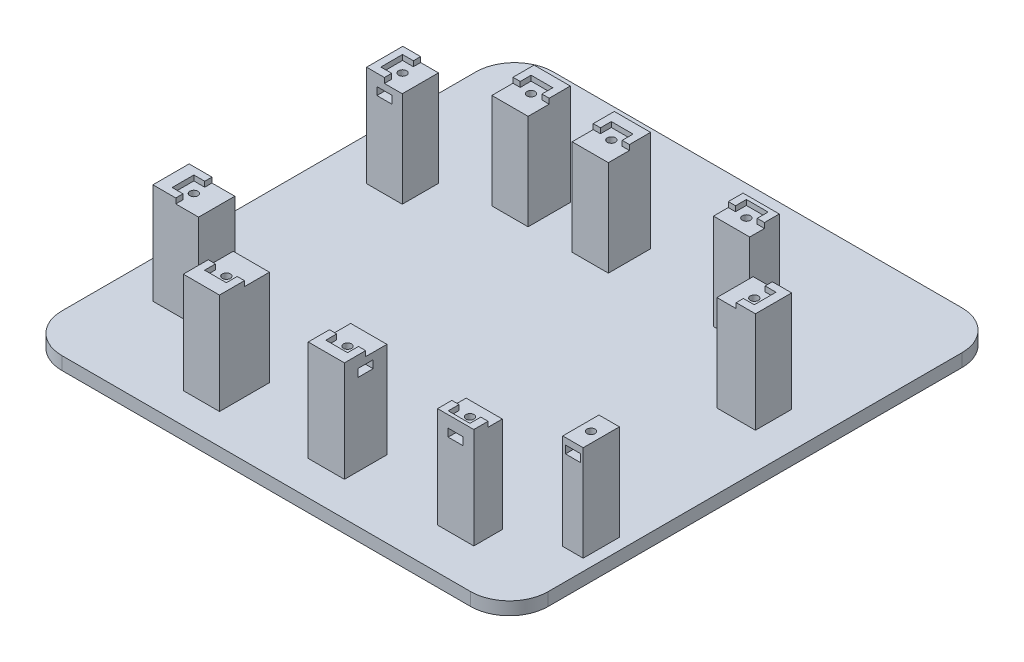
SolidWorks part; units mm, degrees
ref_plane "Front Plane" through (0, 0, 0) normal (0, 0, 1) x (1, 0, 0)
ref_plane "Top Plane" through (0, 0, 0) normal (0, 1, 0) x (1, 0, 0)
ref_plane "Right Plane" through (0, 0, 0) normal (1, 0, 0) x (0, 0, -1)
sketch "Sketch4" plane through (0, 0, 0) normal (0, 1, 0) x (1, 0, 0)
  line L1 (-79, -95) -> (79, -95)
  line L2 (-94, -80) -> (-94, 80)
  line L3 (-79, 95) -> (79, 95)
  line L4 (94, -80) -> (94, 80)
  line L5 (-94, -95) -> (94, 95) construction
  line L6 (-94, 95) -> (94, -95) construction
  arc A0 (79, -95) -> (94, -80) centre (79, -80) ccw
  arc A1 (79, 95) -> (94, 80) centre (79, 80) cw
  arc A2 (-94, 80) -> (-79, 95) centre (-79, 80) cw
  arc A3 (-79, -95) -> (-94, -80) centre (-79, -80) cw
  point P0 (0, 0)
  point P2 (0, 0)
  point P7 (0, 0)
  dimension "D3" = 15
  dimension "D1" = 188
  dimension "D2" = 190
extrude "Boss-Extrude3" add sketch "Sketch4" against normal blind 5 from offset 60 offset against normal yes
sketch "Sketch6" plane through (0, -60, 0) normal (0, 1, 0) x (1, 0, 0)
  line L4 (-74.8, -56.2068) -> (-66.8, -56.2068)
  line L5 (-74.8, -48.2068) -> (-74.8, -56.2068)
  line L6 (-66.8, -48.2068) -> (-74.8, -48.2068)
  line L7 (-66.8, -56.2068) -> (-66.8, -48.2068)
  line L8 (-74.8, -56.2068) -> (-66.8, -56.2068) construction
  line L9 (-74.8, -48.2068) -> (-74.8, -56.2068) construction
  line L10 (-66.8, -48.2068) -> (-74.8, -48.2068) construction
  line L11 (-66.8, -56.2068) -> (-66.8, -48.2068) construction
  line L12 (-32.835, -69.606) -> (-40.835, -69.606)
  line L13 (-40.835, -69.606) -> (-40.835, -77.606)
  line L14 (-40.835, -77.606) -> (-32.835, -77.606)
  line L15 (-32.835, -77.606) -> (-32.835, -69.606)
  line L16 (-32.835, -69.606) -> (-40.835, -69.606) construction
  line L17 (-40.835, -69.606) -> (-40.835, -77.606) construction
  line L18 (-40.835, -77.606) -> (-32.835, -77.606) construction
  line L19 (-32.835, -77.606) -> (-32.835, -69.606) construction
  line L20 (40.2273, 42.394) -> (48.2273, 42.394)
  line L21 (48.2273, 42.394) -> (48.2273, 50.394)
  line L22 (48.2273, 50.394) -> (40.2273, 50.394)
  line L23 (40.2273, 50.394) -> (40.2273, 42.394)
  line L24 (40.2273, 42.394) -> (48.2273, 42.394) construction
  line L25 (48.2273, 42.394) -> (48.2273, 50.394) construction
  line L26 (48.2273, 50.394) -> (40.2273, 50.394) construction
  line L27 (40.2273, 50.394) -> (40.2273, 42.394) construction
  line L28 (-11.9881, 42.394) -> (-3.9881, 42.394)
  line L29 (-3.9881, 42.394) -> (-3.9881, 50.394)
  line L30 (-3.9881, 50.394) -> (-11.9881, 50.394)
  line L31 (-11.9881, 50.394) -> (-11.9881, 42.394)
  line L32 (-11.9881, 42.394) -> (-3.9881, 42.394) construction
  line L33 (-3.9881, 42.394) -> (-3.9881, 50.394) construction
  line L34 (-3.9881, 50.394) -> (-11.9881, 50.394) construction
  line L35 (-11.9881, 50.394) -> (-11.9881, 42.394) construction
  line L36 (-43.0203, 42.394) -> (-35.0203, 42.394)
  line L37 (-35.0203, 42.394) -> (-35.0203, 50.394)
  line L38 (-35.0203, 50.394) -> (-43.0203, 50.394)
  line L39 (-43.0203, 50.394) -> (-43.0203, 42.394)
  line L40 (-43.0203, 42.394) -> (-35.0203, 42.394) construction
  line L41 (-35.0203, 42.394) -> (-35.0203, 50.394) construction
  line L42 (-35.0203, 50.394) -> (-43.0203, 50.394) construction
  line L43 (-43.0203, 50.394) -> (-43.0203, 42.394) construction
  line L44 (-74.8, 24.4768) -> (-66.8, 24.4768)
  line L45 (-66.8, 24.4768) -> (-66.8, 32.4768)
  line L46 (-66.8, 32.4768) -> (-74.8, 32.4768)
  line L47 (-74.8, 32.4768) -> (-74.8, 24.4768)
  line L48 (-74.8, 24.4768) -> (-66.8, 24.4768) construction
  line L49 (-66.8, 24.4768) -> (-66.8, 32.4768) construction
  line L50 (-66.8, 32.4768) -> (-74.8, 32.4768) construction
  line L51 (-74.8, 32.4768) -> (-74.8, 24.4768) construction
  line L52 (61.3476, -69.606) -> (53.3476, -69.606)
  line L53 (53.3476, -69.606) -> (53.3476, -77.606)
  line L54 (53.3476, -77.606) -> (61.3476, -77.606)
  line L55 (61.3476, -77.606) -> (61.3476, -69.606)
  line L56 (61.3476, -69.606) -> (53.3476, -69.606) construction
  line L57 (53.3476, -69.606) -> (53.3476, -77.606) construction
  line L58 (53.3476, -77.606) -> (61.3476, -77.606) construction
  line L59 (61.3476, -77.606) -> (61.3476, -69.606) construction
  line L60 (89.64, -51.0681) -> (81.64, -51.0681)
  line L61 (89.64, -59.0681) -> (89.64, -51.0681)
  line L62 (81.64, -59.0681) -> (89.64, -59.0681)
  line L63 (81.64, -51.0681) -> (81.64, -59.0681)
  line L64 (89.64, -51.0681) -> (81.64, -51.0681) construction
  line L65 (89.64, -59.0681) -> (89.64, -51.0681) construction
  line L66 (81.64, -59.0681) -> (89.64, -59.0681) construction
  line L67 (81.64, -51.0681) -> (81.64, -59.0681) construction
  line L68 (76.6, 25.0765) -> (68.6, 25.0765)
  line L69 (68.6, 25.0765) -> (68.6, 17.0765)
  line L70 (68.6, 17.0765) -> (76.6, 17.0765)
  line L71 (76.6, 17.0765) -> (76.6, 25.0765)
  line L72 (76.6, 25.0765) -> (68.6, 25.0765) construction
  line L73 (68.6, 25.0765) -> (68.6, 17.0765) construction
  line L74 (68.6, 17.0765) -> (76.6, 17.0765) construction
  line L75 (76.6, 17.0765) -> (76.6, 25.0765) construction
  line L76 (14.0236, -69.606) -> (6.0236, -69.606)
  line L77 (14.0236, -77.606) -> (14.0236, -69.606)
  line L78 (6.0236, -77.606) -> (14.0236, -77.606)
  line L79 (6.0236, -69.606) -> (6.0236, -77.606)
  line L80 (14.0236, -69.606) -> (6.0236, -69.606) construction
  line L81 (14.0236, -77.606) -> (14.0236, -69.606) construction
  line L82 (6.0236, -77.606) -> (14.0236, -77.606) construction
  line L83 (6.0236, -69.606) -> (6.0236, -77.606) construction
  line L91 (-63.9015, 21.4768) -> (-77.6985, 21.4768)
  line L92 (-63.9015, 21.4768) -> (-63.9015, 35.4768)
  line L93 (-63.9015, 35.4768) -> (-77.6985, 35.4768)
  line L94 (-77.6985, 21.4768) -> (-77.6985, 35.4768)
  line L95 (-63.9015, 21.4768) -> (-77.6985, 35.4768) construction
  line L96 (-63.9015, 35.4768) -> (-77.6985, 21.4768) construction
  line L97 (-46.0203, 38.2406) -> (-32.0203, 38.2406)
  line L98 (-46.0203, 38.2406) -> (-46.0203, 54.5475)
  line L99 (-46.0203, 54.5475) -> (-32.0203, 54.5475)
  line L100 (-32.0203, 38.2406) -> (-32.0203, 54.5475)
  line L101 (-46.0203, 38.2406) -> (-32.0203, 54.5475) construction
  line L102 (-46.0203, 54.5475) -> (-32.0203, 38.2406) construction
  line L103 (-0.9881, 38.2406) -> (-14.9881, 38.2406)
  line L104 (-0.9881, 38.2406) -> (-0.9881, 54.5475)
  line L105 (-0.9881, 54.5475) -> (-14.9881, 54.5475)
  line L106 (-14.9881, 38.2406) -> (-14.9881, 54.5475)
  line L107 (-0.9881, 38.2406) -> (-14.9881, 54.5475) construction
  line L108 (-0.9881, 54.5475) -> (-14.9881, 38.2406) construction
  line L109 (51.2273, 40.6839) -> (37.2273, 40.6839)
  line L110 (51.2273, 40.6839) -> (51.2273, 52.1042)
  line L111 (51.2273, 52.1042) -> (37.2273, 52.1042)
  line L112 (37.2273, 40.6839) -> (37.2273, 52.1042)
  line L113 (51.2273, 40.6839) -> (37.2273, 52.1042) construction
  line L114 (51.2273, 52.1042) -> (37.2273, 40.6839) construction
  line L115 (65.1552, 14.0765) -> (80.0448, 14.0765)
  line L116 (65.1552, 14.0765) -> (65.1552, 28.0765)
  line L117 (65.1552, 28.0765) -> (80.0448, 28.0765)
  line L118 (80.0448, 14.0765) -> (80.0448, 28.0765)
  line L119 (65.1552, 14.0765) -> (80.0448, 28.0765) construction
  line L120 (65.1552, 28.0765) -> (80.0448, 14.0765) construction
  line L121 (89.5916, -62.0681) -> (81.6884, -62.0681)
  line L122 (89.5916, -62.0681) -> (89.5916, -48.0681)
  line L123 (89.5916, -48.0681) -> (81.6884, -48.0681)
  line L124 (81.6884, -62.0681) -> (81.6884, -48.0681)
  line L125 (89.5916, -62.0681) -> (81.6884, -48.0681) construction
  line L126 (89.5916, -48.0681) -> (81.6884, -62.0681) construction
  line L127 (50.3476, -68.0854) -> (64.3476, -68.0854)
  line L128 (50.3476, -68.0854) -> (50.3476, -79.1265)
  line L129 (50.3476, -79.1265) -> (64.3476, -79.1265)
  line L130 (64.3476, -68.0854) -> (64.3476, -79.1265)
  line L131 (50.3476, -68.0854) -> (64.3476, -79.1265) construction
  line L132 (50.3476, -79.1265) -> (64.3476, -68.0854) construction
  line L133 (3.0236, -65.3947) -> (17.0236, -65.3947)
  line L134 (3.0236, -65.3947) -> (3.0236, -81.8172)
  line L135 (3.0236, -81.8172) -> (17.0236, -81.8172)
  line L136 (17.0236, -65.3947) -> (17.0236, -81.8172)
  line L137 (3.0236, -65.3947) -> (17.0236, -81.8172) construction
  line L138 (3.0236, -81.8172) -> (17.0236, -65.3947) construction
  line L139 (-43.835, -83.2611) -> (-29.835, -83.2611)
  line L140 (-43.835, -83.2611) -> (-43.835, -63.9508)
  line L141 (-43.835, -63.9508) -> (-29.835, -63.9508)
  line L142 (-29.835, -83.2611) -> (-29.835, -63.9508)
  line L143 (-43.835, -83.2611) -> (-29.835, -63.9508) construction
  line L144 (-43.835, -63.9508) -> (-29.835, -83.2611) construction
  line L145 (-79.6301, -59.2068) -> (-61.9699, -59.2068)
  line L146 (-79.6301, -59.2068) -> (-79.6301, -45.2068)
  line L147 (-79.6301, -45.2068) -> (-61.9699, -45.2068)
  line L148 (-61.9699, -59.2068) -> (-61.9699, -45.2068)
  line L149 (-79.6301, -59.2068) -> (-61.9699, -45.2068) construction
  line L150 (-79.6301, -45.2068) -> (-61.9699, -59.2068) construction
  circle A1 centre (-36.835, -73.606) radius 1.55
  circle A2 centre (-36.835, -73.606) radius 1.55 construction
  circle A3 centre (-39.0203, 46.394) radius 1.55
  circle A4 centre (-39.0203, 46.394) radius 1.55 construction
  circle A5 centre (-7.9881, 46.394) radius 1.55
  circle A6 centre (-7.9881, 46.394) radius 1.55 construction
  circle A7 centre (44.2273, 46.394) radius 1.55
  circle A8 centre (44.2273, 46.394) radius 1.55 construction
  circle A9 centre (72.6, 21.0765) radius 1.55
  circle A10 centre (72.6, 21.0765) radius 1.55 construction
  circle A11 centre (85.64, -55.0681) radius 1.55
  circle A12 centre (85.64, -55.0681) radius 1.55 construction
  circle A13 centre (57.3476, -73.606) radius 1.55
  circle A14 centre (57.3476, -73.606) radius 1.55 construction
  circle A15 centre (10.0236, -73.606) radius 1.55
  circle A16 centre (10.0236, -73.606) radius 1.55 construction
  circle A17 centre (-70.8, -52.2068) radius 1.55
  circle A18 centre (-70.8, -52.2068) radius 1.55 construction
  circle A19 centre (-70.8, 28.4768) radius 1.55
  circle A20 centre (-70.8, 28.4768) radius 1.55 construction
  point P73 (-39.0203, 42.394)
  point P76 (-7.9881, 42.394)
  point P79 (44.2273, 42.394)
  point P82 (68.6, 21.0765)
  point P85 (81.64, -55.0681)
  point P88 (57.3476, -69.606)
  point P91 (10.0236, -69.606)
  point P94 (-36.835, -69.606)
  point P97 (-66.8, -52.2068)
  point P100 (-66.8, 28.4768)
  dimension "D21" = 14
  dimension "D1" = 0
  dimension "D2" = 0
  dimension "D3" = 0
  dimension "D4" = 0
  dimension "D5" = 0
  dimension "D6" = 0
  dimension "D7" = 0
  dimension "D8" = 0
  dimension "D9" = 0
  dimension "D10" = 0
  dimension "D11" = 0
  dimension "D12" = 0
  dimension "D13" = 0
  dimension "D14" = 0
  dimension "D15" = 0
  dimension "D16" = 0
  dimension "D17" = 0
  dimension "D18" = 0
  dimension "D19" = 0
  dimension "D20" = 0
extrude "Boss-Extrude4" add sketch "Sketch6" along normal up to surface (37 mm away)
sketch "Sketch7" plane through (0, -23, 0) normal (0, 1, 0) x (1, 0, 0)
  line L0 (-75, -56.4068) -> (-66.6, -56.4068)
  line L1 (-66.6, -56.4068) -> (-66.6, -48.0068)
  line L2 (-66.6, -48.0068) -> (-75, -48.0068)
  line L3 (-75, -48.0068) -> (-75, -56.4068)
  line L4 (-74.8, -56.2068) -> (-66.8, -56.2068)
  line L5 (-74.8, -48.2068) -> (-74.8, -56.2068)
  line L6 (-66.8, -48.2068) -> (-74.8, -48.2068)
  line L7 (-66.8, -56.2068) -> (-66.8, -48.2068)
  line L8 (-74.8, -56.2068) -> (-66.8, -56.2068) construction
  line L9 (-74.8, -48.2068) -> (-74.8, -56.2068) construction
  line L10 (-66.8, -48.2068) -> (-74.8, -48.2068) construction
  line L11 (-66.8, -56.2068) -> (-66.8, -48.2068) construction
  line L12 (-32.835, -69.606) -> (-40.835, -69.606)
  line L13 (-40.835, -69.606) -> (-40.835, -77.606)
  line L14 (-40.835, -77.606) -> (-32.835, -77.606)
  line L15 (-32.835, -77.606) -> (-32.835, -69.606)
  line L16 (-32.835, -69.606) -> (-40.835, -69.606) construction
  line L17 (-40.835, -69.606) -> (-40.835, -77.606) construction
  line L18 (-40.835, -77.606) -> (-32.835, -77.606) construction
  line L19 (-32.835, -77.606) -> (-32.835, -69.606) construction
  line L20 (40.2273, 42.394) -> (48.2273, 42.394)
  line L21 (48.2273, 42.394) -> (48.2273, 50.394)
  line L22 (48.2273, 50.394) -> (40.2273, 50.394)
  line L23 (40.2273, 50.394) -> (40.2273, 42.394)
  line L24 (40.2273, 42.394) -> (48.2273, 42.394) construction
  line L25 (48.2273, 42.394) -> (48.2273, 50.394) construction
  line L26 (48.2273, 50.394) -> (40.2273, 50.394) construction
  line L27 (40.2273, 50.394) -> (40.2273, 42.394) construction
  line L28 (-11.9881, 42.394) -> (-3.9881, 42.394)
  line L29 (-3.9881, 42.394) -> (-3.9881, 50.394)
  line L30 (-3.9881, 50.394) -> (-11.9881, 50.394)
  line L31 (-11.9881, 50.394) -> (-11.9881, 42.394)
  line L32 (-11.9881, 42.394) -> (-3.9881, 42.394) construction
  line L33 (-3.9881, 42.394) -> (-3.9881, 50.394) construction
  line L34 (-3.9881, 50.394) -> (-11.9881, 50.394) construction
  line L35 (-11.9881, 50.394) -> (-11.9881, 42.394) construction
  line L36 (-43.0203, 42.394) -> (-35.0203, 42.394)
  line L37 (-35.0203, 42.394) -> (-35.0203, 50.394)
  line L38 (-35.0203, 50.394) -> (-43.0203, 50.394)
  line L39 (-43.0203, 50.394) -> (-43.0203, 42.394)
  line L40 (-43.0203, 42.394) -> (-35.0203, 42.394) construction
  line L41 (-35.0203, 42.394) -> (-35.0203, 50.394) construction
  line L42 (-35.0203, 50.394) -> (-43.0203, 50.394) construction
  line L43 (-43.0203, 50.394) -> (-43.0203, 42.394) construction
  line L44 (-74.8, 24.4768) -> (-66.8, 24.4768)
  line L45 (-66.8, 24.4768) -> (-66.8, 32.4768)
  line L46 (-66.8, 32.4768) -> (-74.8, 32.4768)
  line L47 (-74.8, 32.4768) -> (-74.8, 24.4768)
  line L48 (-74.8, 24.4768) -> (-66.8, 24.4768) construction
  line L49 (-66.8, 24.4768) -> (-66.8, 32.4768) construction
  line L50 (-66.8, 32.4768) -> (-74.8, 32.4768) construction
  line L51 (-74.8, 32.4768) -> (-74.8, 24.4768) construction
  line L52 (61.3476, -69.606) -> (53.3476, -69.606)
  line L53 (53.3476, -69.606) -> (53.3476, -77.606)
  line L54 (53.3476, -77.606) -> (61.3476, -77.606)
  line L55 (61.3476, -77.606) -> (61.3476, -69.606)
  line L56 (61.3476, -69.606) -> (53.3476, -69.606) construction
  line L57 (53.3476, -69.606) -> (53.3476, -77.606) construction
  line L58 (53.3476, -77.606) -> (61.3476, -77.606) construction
  line L59 (61.3476, -77.606) -> (61.3476, -69.606) construction
  line L60 (89.64, -51.0681) -> (81.64, -51.0681)
  line L61 (89.64, -59.0681) -> (89.64, -51.0681)
  line L62 (81.64, -59.0681) -> (89.64, -59.0681)
  line L63 (81.64, -51.0681) -> (81.64, -59.0681)
  line L64 (89.64, -51.0681) -> (81.64, -51.0681) construction
  line L65 (89.64, -59.0681) -> (89.64, -51.0681) construction
  line L66 (81.64, -59.0681) -> (89.64, -59.0681) construction
  line L67 (81.64, -51.0681) -> (81.64, -59.0681) construction
  line L68 (76.6, 25.0765) -> (68.6, 25.0765)
  line L69 (68.6, 25.0765) -> (68.6, 17.0765)
  line L70 (68.6, 17.0765) -> (76.6, 17.0765)
  line L71 (76.6, 17.0765) -> (76.6, 25.0765)
  line L72 (76.6, 25.0765) -> (68.6, 25.0765) construction
  line L73 (68.6, 25.0765) -> (68.6, 17.0765) construction
  line L74 (68.6, 17.0765) -> (76.6, 17.0765) construction
  line L75 (76.6, 17.0765) -> (76.6, 25.0765) construction
  line L76 (14.0236, -69.606) -> (6.0236, -69.606)
  line L77 (14.0236, -77.606) -> (14.0236, -69.606)
  line L78 (6.0236, -77.606) -> (14.0236, -77.606)
  line L79 (6.0236, -69.606) -> (6.0236, -77.606)
  line L80 (14.0236, -69.606) -> (6.0236, -69.606) construction
  line L81 (14.0236, -77.606) -> (14.0236, -69.606) construction
  line L82 (6.0236, -77.606) -> (14.0236, -77.606) construction
  line L83 (6.0236, -69.606) -> (6.0236, -77.606) construction
  line L84 (-32.635, -69.406) -> (-41.035, -69.406) construction
  line L85 (-41.035, -69.406) -> (-41.035, -77.806)
  line L86 (-41.035, -77.806) -> (-32.635, -77.806)
  line L87 (-32.635, -77.806) -> (-32.635, -69.406)
  line L88 (40.0273, 42.194) -> (48.4273, 42.194)
  line L89 (48.4273, 42.194) -> (48.4273, 50.594)
  line L90 (48.4273, 50.594) -> (40.0273, 50.594)
  line L91 (40.0273, 50.594) -> (40.0273, 42.194)
  line L92 (-12.1881, 42.194) -> (-3.7881, 42.194)
  line L93 (-3.7881, 42.194) -> (-3.7881, 50.594)
  line L94 (-3.7881, 50.594) -> (-12.1881, 50.594)
  line L95 (-12.1881, 50.594) -> (-12.1881, 42.194)
  line L96 (-43.2203, 42.194) -> (-34.8203, 42.194)
  line L97 (-34.8203, 42.194) -> (-34.8203, 50.594)
  line L98 (-34.8203, 50.594) -> (-43.2203, 50.594)
  line L99 (-43.2203, 50.594) -> (-43.2203, 42.194)
  line L100 (-75, 24.2768) -> (-66.6, 24.2768)
  line L101 (-66.6, 24.2768) -> (-66.6, 32.6768)
  line L102 (-66.6, 32.6768) -> (-75, 32.6768)
  line L103 (-75, 32.6768) -> (-75, 24.2768)
  line L104 (61.5476, -69.406) -> (53.1476, -69.406)
  line L105 (53.1476, -69.406) -> (53.1476, -77.806)
  line L106 (53.1476, -77.806) -> (61.5476, -77.806)
  line L107 (61.5476, -77.806) -> (61.5476, -69.406)
  line L108 (89.84, -50.8681) -> (81.44, -50.8681)
  line L109 (81.44, -50.8681) -> (81.44, -59.2681)
  line L110 (81.44, -59.2681) -> (89.84, -59.2681)
  line L111 (89.84, -59.2681) -> (89.84, -50.8681)
  line L112 (76.8, 25.2765) -> (68.4, 25.2765)
  line L113 (68.4, 25.2765) -> (68.4, 16.8765)
  line L114 (68.4, 16.8765) -> (76.8, 16.8765)
  line L115 (76.8, 16.8765) -> (76.8, 25.2765)
  line L116 (14.2236, -69.406) -> (5.8236, -69.406)
  line L117 (5.8236, -69.406) -> (5.8236, -77.806)
  line L118 (5.8236, -77.806) -> (14.2236, -77.806)
  line L119 (14.2236, -77.806) -> (14.2236, -69.406)
  line L120 (65.1552, 14.0765) -> (80.0448, 14.0765) construction
  line L121 (80.0448, 14.0765) -> (80.0448, 28.0765) construction
  line L122 (80.0448, 28.0765) -> (65.1552, 28.0765) construction
  line L123 (65.1552, 28.0765) -> (65.1552, 14.0765) construction
  line L124 (51.2273, 52.1042) -> (37.2273, 52.1042) construction
  line L125 (37.2273, 52.1042) -> (37.2273, 40.6839) construction
  line L126 (37.2273, 40.6839) -> (51.2273, 40.6839) construction
  line L127 (51.2273, 40.6839) -> (51.2273, 52.1042) construction
  line L128 (-0.9881, 54.5475) -> (-14.9881, 54.5475) construction
  line L129 (-14.9881, 54.5475) -> (-14.9881, 38.2406) construction
  line L130 (-14.9881, 38.2406) -> (-0.9881, 38.2406) construction
  line L131 (-0.9881, 38.2406) -> (-0.9881, 54.5475) construction
  line L132 (-46.0203, 38.2406) -> (-32.0203, 38.2406) construction
  line L133 (-32.0203, 38.2406) -> (-32.0203, 54.5475) construction
  line L134 (-32.0203, 54.5475) -> (-46.0203, 54.5475) construction
  line L135 (-46.0203, 54.5475) -> (-46.0203, 38.2406) construction
  line L136 (-63.9015, 35.4768) -> (-77.6985, 35.4768) construction
  line L137 (-77.6985, 35.4768) -> (-77.6985, 21.4768) construction
  line L138 (-77.6985, 21.4768) -> (-63.9015, 21.4768) construction
  line L139 (-63.9015, 21.4768) -> (-63.9015, 35.4768) construction
  line L140 (-79.6301, -59.2068) -> (-61.9699, -59.2068) construction
  line L141 (-61.9699, -59.2068) -> (-61.9699, -45.2068) construction
  line L142 (-61.9699, -45.2068) -> (-79.6301, -45.2068) construction
  line L143 (-79.6301, -45.2068) -> (-79.6301, -59.2068) construction
  line L144 (-43.835, -83.2611) -> (-29.835, -83.2611) construction
  line L145 (-29.835, -83.2611) -> (-29.835, -63.9508) construction
  line L146 (-29.835, -63.9508) -> (-43.835, -63.9508) construction
  line L147 (-43.835, -63.9508) -> (-43.835, -83.2611) construction
  line L148 (89.5916, -48.0681) -> (81.6884, -48.0681) construction
  line L149 (81.6884, -48.0681) -> (81.6884, -62.0681) construction
  line L150 (81.6884, -62.0681) -> (89.5916, -62.0681) construction
  line L151 (89.5916, -62.0681) -> (89.5916, -48.0681) construction
  line L152 (50.3476, -79.1265) -> (64.3476, -79.1265) construction
  line L153 (64.3476, -79.1265) -> (64.3476, -68.0854) construction
  line L154 (64.3476, -68.0854) -> (50.3476, -68.0854) construction
  line L155 (50.3476, -68.0854) -> (50.3476, -79.1265) construction
  line L156 (3.0236, -81.8172) -> (17.0236, -81.8172) construction
  line L157 (17.0236, -81.8172) -> (17.0236, -65.3947) construction
  line L158 (17.0236, -65.3947) -> (3.0236, -65.3947) construction
  line L159 (3.0236, -65.3947) -> (3.0236, -81.8172) construction
  line L160 (65.1552, 14.0765) -> (80.0448, 14.0765)
  line L161 (80.0448, 14.0765) -> (80.0448, 28.0765)
  line L162 (80.0448, 28.0765) -> (65.1552, 28.0765)
  line L163 (65.1552, 28.0765) -> (65.1552, 14.0765)
  line L164 (51.2273, 52.1042) -> (37.2273, 52.1042)
  line L165 (37.2273, 52.1042) -> (37.2273, 40.6839)
  line L166 (37.2273, 40.6839) -> (51.2273, 40.6839)
  line L167 (51.2273, 40.6839) -> (51.2273, 52.1042)
  line L168 (-0.9881, 54.5475) -> (-14.9881, 54.5475)
  line L169 (-14.9881, 54.5475) -> (-14.9881, 38.2406)
  line L170 (-14.9881, 38.2406) -> (-0.9881, 38.2406)
  line L171 (-0.9881, 38.2406) -> (-0.9881, 54.5475)
  line L172 (-46.0203, 38.2406) -> (-32.0203, 38.2406)
  line L173 (-32.0203, 38.2406) -> (-32.0203, 54.5475)
  line L174 (-32.0203, 54.5475) -> (-46.0203, 54.5475)
  line L175 (-46.0203, 54.5475) -> (-46.0203, 38.2406)
  line L176 (-63.9015, 35.4768) -> (-77.6985, 35.4768)
  line L177 (-77.6985, 35.4768) -> (-77.6985, 21.4768)
  line L178 (-77.6985, 21.4768) -> (-63.9015, 21.4768)
  line L179 (-63.9015, 21.4768) -> (-63.9015, 35.4768)
  line L180 (-79.6301, -59.2068) -> (-61.9699, -59.2068)
  line L181 (-61.9699, -59.2068) -> (-61.9699, -45.2068)
  line L182 (-61.9699, -45.2068) -> (-79.6301, -45.2068)
  line L183 (-79.6301, -45.2068) -> (-79.6301, -59.2068)
  line L184 (-43.835, -83.2611) -> (-29.835, -83.2611)
  line L185 (-29.835, -83.2611) -> (-29.835, -63.9508)
  line L186 (-29.835, -63.9508) -> (-43.835, -63.9508) construction
  line L187 (-43.835, -63.9508) -> (-43.835, -83.2611)
  line L188 (89.5916, -48.0681) -> (81.6884, -48.0681)
  line L189 (81.6884, -48.0681) -> (81.6884, -62.0681)
  line L190 (81.6884, -62.0681) -> (89.5916, -62.0681)
  line L191 (89.5916, -62.0681) -> (89.5916, -48.0681)
  line L192 (50.3476, -79.1265) -> (64.3476, -79.1265)
  line L193 (64.3476, -79.1265) -> (64.3476, -68.0854)
  line L194 (64.3476, -68.0854) -> (50.3476, -68.0854)
  line L195 (50.3476, -68.0854) -> (50.3476, -79.1265)
  line L196 (3.0236, -81.8172) -> (17.0236, -81.8172)
  line L197 (17.0236, -81.8172) -> (17.0236, -65.3947)
  line L198 (17.0236, -65.3947) -> (3.0236, -65.3947)
  line L199 (3.0236, -65.3947) -> (3.0236, -81.8172)
  line L200 (-41.035, -73.606) -> (-43.835, -73.606)
  line L201 (-32.635, -73.606) -> (-29.835, -73.606)
  line L202 (3.0236, -73.606) -> (5.8236, -73.606)
  line L203 (14.2236, -73.606) -> (17.0236, -73.606)
  line L204 (50.3476, -73.606) -> (53.1476, -73.606)
  line L205 (61.5476, -73.606) -> (64.3476, -73.606)
  line L206 (85.64, -59.2681) -> (85.64, -62.0681)
  line L207 (85.64, -50.8681) -> (85.64, -48.0681)
  line L208 (72.6, 14.0765) -> (72.6, 16.8765)
  line L209 (72.6, 25.2765) -> (72.6, 28.0765)
  line L210 (51.2273, 46.394) -> (48.4273, 46.394)
  line L211 (40.0273, 46.394) -> (37.2273, 46.394)
  line L212 (-0.9881, 46.394) -> (-3.7881, 46.394)
  line L213 (-12.1881, 46.394) -> (-14.9881, 46.394)
  line L214 (-32.0203, 46.394) -> (-34.8203, 46.394)
  line L215 (-43.2203, 46.394) -> (-46.0203, 46.394)
  line L216 (-70.8, 35.4768) -> (-70.8, 32.6768)
  line L217 (-70.8, 24.2768) -> (-70.8, 21.4768)
  line L218 (-70.8, -45.2068) -> (-70.8, -48.0068)
  line L219 (-70.8, -56.4068) -> (-70.8, -59.2068)
  circle A1 centre (-36.835, -73.606) radius 1.55
  circle A2 centre (-36.835, -73.606) radius 1.55 construction
  circle A3 centre (-39.0203, 46.394) radius 1.55
  circle A4 centre (-39.0203, 46.394) radius 1.55 construction
  circle A5 centre (-7.9881, 46.394) radius 1.55
  circle A6 centre (-7.9881, 46.394) radius 1.55 construction
  circle A7 centre (44.2273, 46.394) radius 1.55
  circle A8 centre (44.2273, 46.394) radius 1.55 construction
  circle A9 centre (72.6, 21.0765) radius 1.55
  circle A10 centre (72.6, 21.0765) radius 1.55 construction
  circle A11 centre (85.64, -55.0681) radius 1.55
  circle A12 centre (85.64, -55.0681) radius 1.55 construction
  circle A13 centre (57.3476, -73.606) radius 1.55
  circle A14 centre (57.3476, -73.606) radius 1.55 construction
  circle A15 centre (10.0236, -73.606) radius 1.55
  circle A16 centre (10.0236, -73.606) radius 1.55 construction
  circle A17 centre (-70.8, -52.2068) radius 1.55
  circle A18 centre (-70.8, -52.2068) radius 1.55 construction
  circle A19 centre (-70.8, 28.4768) radius 1.55
  circle A20 centre (-70.8, 28.4768) radius 1.55 construction
  dimension "D1" = 0
  dimension "D2" = 0
  dimension "D3" = 0
  dimension "D4" = 0
  dimension "D5" = 0
  dimension "D6" = 0
  dimension "D7" = 0
  dimension "D8" = 0
  dimension "D9" = 0
  dimension "D10" = 0
  dimension "D11" = 0
  dimension "D12" = 0
  dimension "D13" = 0
  dimension "D14" = 0
  dimension "D15" = 0
  dimension "D16" = 0
  dimension "D17" = 0
  dimension "D18" = 0
  dimension "D19" = 0
  dimension "D20" = 0
  dimension "D21" = 0.2
extrude "Boss-Extrude5" add sketch "Sketch7" along normal blind 2 contours L201 L87 L86 L85 L200 L187 L184 L185 | L203 L119 L118 L117 L202 L199 L196 L197 | L205 L107 L106 L105 L204 L195 L192 L193 | L209 L112 L115 L114 L208 L160 L161 L162 | L211 L91 L90 L89 L210 L167 L164 L165 | L213 L95 L94 L93 L212 L171 L168 L169 | L217 L100 L103 L102 L216 L176 L177 L178 | L219 L0 L3 L2 L218 L182 L183 L180 | L215 L99 L98 L97 L214 L173 L174 L175 region at (-76.1396, -23, 52.2068) region at (-36.835, -23, 79.3969) region at (38.6273, -23, -46.5452) region at (-7.9881, -23, -51.355) region at (-39.0203, -23, -51.355) region at (-75.0258, -23, -28.4768) region at (62.9476, -23, 73.7564) region at (77.1526, -23, -21.0765) region at (10.0236, -23, 78.5996)
sketch "Sketch8" plane through (0, -23, 0) normal (0, 1, 0) x (1, 0, 0)
  line L4 (-74.8, -56.2068) -> (-66.8, -56.2068)
  line L5 (-74.8, -48.2068) -> (-74.8, -56.2068)
  line L6 (-66.8, -48.2068) -> (-74.8, -48.2068)
  line L7 (-66.8, -56.2068) -> (-66.8, -48.2068)
  line L8 (-74.8, -56.2068) -> (-66.8, -56.2068) construction
  line L9 (-74.8, -48.2068) -> (-74.8, -56.2068) construction
  line L10 (-66.8, -48.2068) -> (-74.8, -48.2068) construction
  line L11 (-66.8, -56.2068) -> (-66.8, -48.2068) construction
  line L12 (-32.835, -69.606) -> (-40.835, -69.606)
  line L13 (-40.835, -69.606) -> (-40.835, -77.606)
  line L14 (-40.835, -77.606) -> (-32.835, -77.606)
  line L15 (-32.835, -77.606) -> (-32.835, -69.606)
  line L16 (-32.835, -69.606) -> (-40.835, -69.606) construction
  line L17 (-40.835, -69.606) -> (-40.835, -77.606) construction
  line L18 (-40.835, -77.606) -> (-32.835, -77.606) construction
  line L19 (-32.835, -77.606) -> (-32.835, -69.606) construction
  line L20 (40.2273, 42.394) -> (48.2273, 42.394)
  line L21 (48.2273, 42.394) -> (48.2273, 50.394)
  line L22 (48.2273, 50.394) -> (40.2273, 50.394)
  line L23 (40.2273, 50.394) -> (40.2273, 42.394)
  line L24 (40.2273, 42.394) -> (48.2273, 42.394) construction
  line L25 (48.2273, 42.394) -> (48.2273, 50.394) construction
  line L26 (48.2273, 50.394) -> (40.2273, 50.394) construction
  line L27 (40.2273, 50.394) -> (40.2273, 42.394) construction
  line L28 (-11.9881, 42.394) -> (-3.9881, 42.394)
  line L29 (-3.9881, 42.394) -> (-3.9881, 50.394)
  line L30 (-3.9881, 50.394) -> (-11.9881, 50.394)
  line L31 (-11.9881, 50.394) -> (-11.9881, 42.394)
  line L32 (-11.9881, 42.394) -> (-3.9881, 42.394) construction
  line L33 (-3.9881, 42.394) -> (-3.9881, 50.394) construction
  line L34 (-3.9881, 50.394) -> (-11.9881, 50.394) construction
  line L35 (-11.9881, 50.394) -> (-11.9881, 42.394) construction
  line L36 (-43.0203, 42.394) -> (-35.0203, 42.394)
  line L37 (-35.0203, 42.394) -> (-35.0203, 50.394)
  line L38 (-35.0203, 50.394) -> (-43.0203, 50.394)
  line L39 (-43.0203, 50.394) -> (-43.0203, 42.394)
  line L40 (-43.0203, 42.394) -> (-35.0203, 42.394) construction
  line L41 (-35.0203, 42.394) -> (-35.0203, 50.394) construction
  line L42 (-35.0203, 50.394) -> (-43.0203, 50.394) construction
  line L43 (-43.0203, 50.394) -> (-43.0203, 42.394) construction
  line L44 (-74.8, 24.4768) -> (-66.8, 24.4768)
  line L45 (-66.8, 24.4768) -> (-66.8, 32.4768)
  line L46 (-66.8, 32.4768) -> (-74.8, 32.4768)
  line L47 (-74.8, 32.4768) -> (-74.8, 24.4768)
  line L48 (-74.8, 24.4768) -> (-66.8, 24.4768) construction
  line L49 (-66.8, 24.4768) -> (-66.8, 32.4768) construction
  line L50 (-66.8, 32.4768) -> (-74.8, 32.4768) construction
  line L51 (-74.8, 32.4768) -> (-74.8, 24.4768) construction
  line L52 (61.3476, -69.606) -> (53.3476, -69.606)
  line L53 (53.3476, -69.606) -> (53.3476, -77.606)
  line L54 (53.3476, -77.606) -> (61.3476, -77.606)
  line L55 (61.3476, -77.606) -> (61.3476, -69.606)
  line L56 (61.3476, -69.606) -> (53.3476, -69.606) construction
  line L57 (53.3476, -69.606) -> (53.3476, -77.606) construction
  line L58 (53.3476, -77.606) -> (61.3476, -77.606) construction
  line L59 (61.3476, -77.606) -> (61.3476, -69.606) construction
  line L60 (89.64, -51.0681) -> (81.64, -51.0681)
  line L61 (89.64, -59.0681) -> (89.64, -51.0681)
  line L62 (81.64, -59.0681) -> (89.64, -59.0681)
  line L63 (81.64, -51.0681) -> (81.64, -59.0681)
  line L64 (89.64, -51.0681) -> (81.64, -51.0681) construction
  line L65 (89.64, -59.0681) -> (89.64, -51.0681) construction
  line L66 (81.64, -59.0681) -> (89.64, -59.0681) construction
  line L67 (81.64, -51.0681) -> (81.64, -59.0681) construction
  line L68 (76.6, 25.0765) -> (68.6, 25.0765)
  line L69 (68.6, 25.0765) -> (68.6, 17.0765)
  line L70 (68.6, 17.0765) -> (76.6, 17.0765)
  line L71 (76.6, 17.0765) -> (76.6, 25.0765)
  line L72 (76.6, 25.0765) -> (68.6, 25.0765) construction
  line L73 (68.6, 25.0765) -> (68.6, 17.0765) construction
  line L74 (68.6, 17.0765) -> (76.6, 17.0765) construction
  line L75 (76.6, 17.0765) -> (76.6, 25.0765) construction
  line L76 (14.0236, -69.606) -> (6.0236, -69.606)
  line L77 (14.0236, -77.606) -> (14.0236, -69.606)
  line L78 (6.0236, -77.606) -> (14.0236, -77.606)
  line L79 (6.0236, -69.606) -> (6.0236, -77.606)
  line L80 (14.0236, -69.606) -> (6.0236, -69.606) construction
  line L81 (14.0236, -77.606) -> (14.0236, -69.606) construction
  line L82 (6.0236, -77.606) -> (14.0236, -77.606) construction
  line L83 (6.0236, -69.606) -> (6.0236, -77.606) construction
  circle A1 centre (-36.835, -73.606) radius 1.55
  circle A2 centre (-36.835, -73.606) radius 1.55
  circle A3 centre (-39.0203, 46.394) radius 1.55
  circle A4 centre (-39.0203, 46.394) radius 1.55
  circle A5 centre (-7.9881, 46.394) radius 1.55
  circle A6 centre (-7.9881, 46.394) radius 1.55
  circle A7 centre (44.2273, 46.394) radius 1.55
  circle A8 centre (44.2273, 46.394) radius 1.55
  circle A9 centre (72.6, 21.0765) radius 1.55
  circle A10 centre (72.6, 21.0765) radius 1.55
  circle A11 centre (85.64, -55.0681) radius 1.55
  circle A12 centre (85.64, -55.0681) radius 1.55
  circle A13 centre (57.3476, -73.606) radius 1.55
  circle A14 centre (57.3476, -73.606) radius 1.55
  circle A15 centre (10.0236, -73.606) radius 1.55
  circle A16 centre (10.0236, -73.606) radius 1.55
  circle A17 centre (-70.8, -52.2068) radius 1.55
  circle A18 centre (-70.8, -52.2068) radius 1.55
  circle A19 centre (-70.8, 28.4768) radius 1.55
  circle A20 centre (-70.8, 28.4768) radius 1.55
  dimension "D1" = 0
  dimension "D2" = 0
  dimension "D3" = 0
  dimension "D4" = 0
  dimension "D5" = 0
  dimension "D6" = 0
  dimension "D7" = 0
  dimension "D8" = 0
  dimension "D9" = 0
  dimension "D10" = 0
  dimension "D11" = 0
  dimension "D12" = 0
  dimension "D13" = 0
  dimension "D14" = 0
  dimension "D15" = 0
  dimension "D16" = 0
  dimension "D17" = 0
  dimension "D18" = 0
  dimension "D19" = 0
  dimension "D20" = 0
extrude "Cut-Extrude1" cut sketch "Sketch8" against normal blind 6
sketch "Sketch9" plane through (0, -23, 0) normal (0, 1, 0) x (1, 0, 0)
  line L0 (-41.9203, 43.494) -> (-36.1203, 49.294) construction
  line L1 (-73.7, 25.5768) -> (-67.9, 25.5768) construction
  line L2 (-73.7, 25.5768) -> (-73.7, 31.3768)
  line L3 (-73.7, 31.3768) -> (-67.9, 31.3768)
  line L4 (-67.9, 25.5768) -> (-67.9, 31.3768)
  line L5 (-73.7, 25.5768) -> (-67.9, 31.3768) construction
  line L6 (-73.7, 31.3768) -> (-67.9, 25.5768) construction
  line L7 (-41.9203, 43.494) -> (-41.9203, 49.294)
  line L8 (-36.1203, 43.494) -> (-36.1203, 49.294)
  line L9 (-41.9203, 43.494) -> (-36.1203, 43.494)
  line L10 (-41.9203, 49.294) -> (-36.1203, 43.494) construction
  line L11 (-41.9203, 49.294) -> (-36.1203, 49.294) construction
  line L12 (-10.8881, 43.494) -> (-10.8881, 49.294)
  line L13 (-10.8881, 49.294) -> (-5.0881, 43.494) construction
  line L14 (-10.8881, 49.294) -> (-5.0881, 49.294) construction
  line L15 (-5.0881, 43.494) -> (-5.0881, 49.294)
  line L16 (-10.8881, 43.494) -> (-5.0881, 43.494)
  line L17 (-10.8881, 43.494) -> (-5.0881, 49.294) construction
  line L18 (41.3273, 43.494) -> (41.3273, 49.294)
  line L19 (41.3273, 49.294) -> (47.1273, 43.494) construction
  line L20 (41.3273, 49.294) -> (47.1273, 49.294) construction
  line L21 (47.1273, 43.494) -> (47.1273, 49.294)
  line L22 (41.3273, 43.494) -> (47.1273, 43.494)
  line L23 (41.3273, 43.494) -> (47.1273, 49.294) construction
  line L24 (69.7, 18.1765) -> (69.7, 23.9765)
  line L25 (69.7, 23.9765) -> (75.5, 18.1765) construction
  line L26 (69.7, 23.9765) -> (75.5, 23.9765) construction
  line L27 (75.5, 18.1765) -> (75.5, 23.9765)
  line L28 (69.7, 18.1765) -> (75.5, 18.1765)
  line L29 (69.7, 18.1765) -> (75.5, 23.9765) construction
  line L30 (82.74, -57.9681) -> (82.74, -52.1681)
  line L31 (82.74, -52.1681) -> (88.54, -57.9681) construction
  line L32 (82.74, -52.1681) -> (88.54, -52.1681)
  line L33 (88.54, -57.9681) -> (88.54, -52.1681)
  line L34 (82.74, -57.9681) -> (88.54, -57.9681) construction
  line L35 (82.74, -57.9681) -> (88.54, -52.1681) construction
  line L36 (54.4476, -76.506) -> (54.4476, -70.706)
  line L37 (54.4476, -70.706) -> (60.2476, -76.506) construction
  line L38 (54.4476, -70.706) -> (60.2476, -70.706)
  line L39 (60.2476, -76.506) -> (60.2476, -70.706)
  line L40 (54.4476, -76.506) -> (60.2476, -76.506) construction
  line L41 (54.4476, -76.506) -> (60.2476, -70.706) construction
  line L42 (7.1236, -76.506) -> (7.1236, -70.706)
  line L43 (7.1236, -70.706) -> (12.9236, -76.506) construction
  line L44 (7.1236, -70.706) -> (12.9236, -70.706)
  line L45 (12.9236, -76.506) -> (12.9236, -70.706) construction
  line L46 (7.1236, -76.506) -> (12.9236, -76.506)
  line L47 (7.1236, -76.506) -> (12.9236, -70.706) construction
  line L49 (-39.735, -70.706) -> (-33.935, -76.506) construction
  line L50 (-39.735, -70.706) -> (-33.935, -70.706)
  line L51 (-33.935, -76.506) -> (-33.935, -70.706)
  line L52 (-39.735, -76.506) -> (-33.935, -76.506)
  line L53 (-39.735, -76.506) -> (-33.935, -70.706) construction
  line L54 (-73.7, -55.1068) -> (-73.7, -49.3068)
  line L55 (-73.7, -49.3068) -> (-67.9, -55.1068) construction
  line L56 (-73.7, -49.3068) -> (-67.9, -49.3068) construction
  line L57 (-67.9, -55.1068) -> (-67.9, -49.3068)
  line L58 (-73.7, -55.1068) -> (-67.9, -55.1068)
  line L59 (-73.7, -55.1068) -> (-67.9, -49.3068) construction
  line L60 (-61.9699, -45.2068) -> (-70.8, -45.2068) construction
  line L61 (-73.7, -49.3068) -> (-67.9, -49.3068) construction
  line L62 (-73.7, -49.3068) -> (-73.7, -45.2068)
  line L63 (-73.7, -45.2068) -> (-67.9, -45.2068)
  line L64 (-67.9, -49.3068) -> (-67.9, -45.2068)
  line L65 (-77.6985, 21.4768) -> (-63.9015, 21.4768) construction
  line L66 (-73.7, 25.5768) -> (-67.9, 25.5768) construction
  line L67 (-73.7, 25.5768) -> (-73.7, 21.4768)
  line L68 (-73.7, 21.4768) -> (-67.9, 21.4768)
  line L69 (-67.9, 25.5768) -> (-67.9, 21.4768)
  line L70 (-32.0203, 54.5475) -> (-46.0203, 54.5475) construction
  line L71 (-41.9203, 49.294) -> (-36.1203, 49.294) construction
  line L72 (-41.9203, 49.294) -> (-41.9203, 54.5475)
  line L73 (-41.9203, 54.5475) -> (-36.1203, 54.5475)
  line L74 (-36.1203, 49.294) -> (-36.1203, 54.5475)
  line L75 (-0.9881, 54.5475) -> (-14.9881, 54.5475) construction
  line L76 (-10.8881, 49.294) -> (-5.0881, 49.294) construction
  line L77 (-10.8881, 49.294) -> (-10.8881, 54.5475)
  line L78 (-10.8881, 54.5475) -> (-5.0881, 54.5475)
  line L79 (-5.0881, 49.294) -> (-5.0881, 54.5475)
  line L80 (51.2273, 52.1042) -> (37.2273, 52.1042) construction
  line L81 (41.3273, 49.294) -> (47.1273, 49.294) construction
  line L82 (41.3273, 49.294) -> (41.3273, 52.1042)
  line L83 (41.3273, 52.1042) -> (47.1273, 52.1042)
  line L84 (47.1273, 49.294) -> (47.1273, 52.1042)
  line L85 (80.0448, 28.0765) -> (65.1552, 28.0765) construction
  line L86 (69.7, 23.9765) -> (75.5, 23.9765) construction
  line L87 (69.7, 23.9765) -> (69.7, 28.0765)
  line L88 (69.7, 28.0765) -> (75.5, 28.0765)
  line L89 (75.5, 23.9765) -> (75.5, 28.0765)
  line L90 (81.6884, -62.0681) -> (89.5916, -62.0681) construction
  line L91 (82.74, -57.9681) -> (88.54, -57.9681) construction
  line L92 (82.74, -57.9681) -> (82.74, -62.0681)
  line L93 (82.74, -62.0681) -> (88.54, -62.0681)
  line L94 (88.54, -57.9681) -> (88.54, -62.0681)
  line L95 (50.3476, -79.1265) -> (64.3476, -79.1265) construction
  line L96 (54.4476, -76.506) -> (60.2476, -76.506) construction
  line L97 (54.4476, -76.506) -> (54.4476, -79.1265)
  line L98 (54.4476, -79.1265) -> (60.2476, -79.1265)
  line L99 (60.2476, -76.506) -> (60.2476, -79.1265)
  line L100 (17.0236, -81.8172) -> (17.0236, -65.3947) construction
  line L101 (12.9236, -70.706) -> (17.0236, -70.706)
  line L102 (12.9236, -70.706) -> (12.9236, -76.506) construction
  line L103 (12.9236, -76.506) -> (17.0236, -76.506)
  line L104 (17.0236, -70.706) -> (17.0236, -76.506)
  line L105 (-43.835, -73.606) -> (-43.835, -83.2611) construction
  line L106 (-39.735, -70.706) -> (-43.835, -70.706)
  line L107 (-39.735, -70.706) -> (-39.735, -76.506) construction
  line L108 (-39.735, -76.506) -> (-43.835, -76.506)
  line L109 (-43.835, -70.706) -> (-43.835, -76.506)
  circle A1 centre (-39.0203, 46.394) radius 1.55
  circle A2 centre (-39.0203, 46.394) radius 1.55 construction
  circle A3 centre (-36.835, -73.606) radius 1.55
  circle A4 centre (-36.835, -73.606) radius 1.55 construction
  circle A5 centre (57.3476, -73.606) radius 1.55
  circle A6 centre (57.3476, -73.606) radius 1.55 construction
  circle A7 centre (85.64, -55.0681) radius 1.55
  circle A8 centre (85.64, -55.0681) radius 1.55 construction
  circle A9 centre (72.6, 21.0765) radius 1.55
  circle A10 centre (72.6, 21.0765) radius 1.55 construction
  circle A11 centre (44.2273, 46.394) radius 1.55
  circle A12 centre (44.2273, 46.394) radius 1.55 construction
  circle A13 centre (-7.9881, 46.394) radius 1.55
  circle A14 centre (-7.9881, 46.394) radius 1.55 construction
  circle A15 centre (-70.8, 28.4768) radius 1.55
  circle A16 centre (-70.8, 28.4768) radius 1.55 construction
  circle A17 centre (-70.8, -52.2068) radius 1.55
  circle A18 centre (-70.8, -52.2068) radius 1.55 construction
  circle A19 centre (10.0236, -73.606) radius 1.55
  circle A20 centre (10.0236, -73.606) radius 1.55 construction
  point P61 (72.6, 21.0765)
  point P66 (85.64, -55.0681)
  point P68 (57.3476, -73.606)
  point P73 (10.0236, -73.606)
  point P79 (-36.835, -73.606)
  point P84 (-70.8, -52.2068)
  point P89 (-7.9881, 46.394)
  dimension "D11" = 5.8
  dimension "D12" = 5.8
  dimension "D13" = 5.8
  dimension "D14" = 5.8
  dimension "D15" = 5.8
  dimension "D16" = 5.8
  dimension "D17" = 5.8
  dimension "D18" = 5.8
  dimension "D19" = 5.8
  dimension "D20" = 5.8
  dimension "D1" = 0
  dimension "D2" = 0
  dimension "D3" = 0
  dimension "D4" = 0
  dimension "D5" = 0
  dimension "D6" = 0
  dimension "D7" = 0
  dimension "D8" = 0
  dimension "D9" = 0
  dimension "D10" = 0
extrude "Cut-Extrude2" cut sketch "Sketch9" against normal blind 3 from offset 2.5 offset against normal yes
